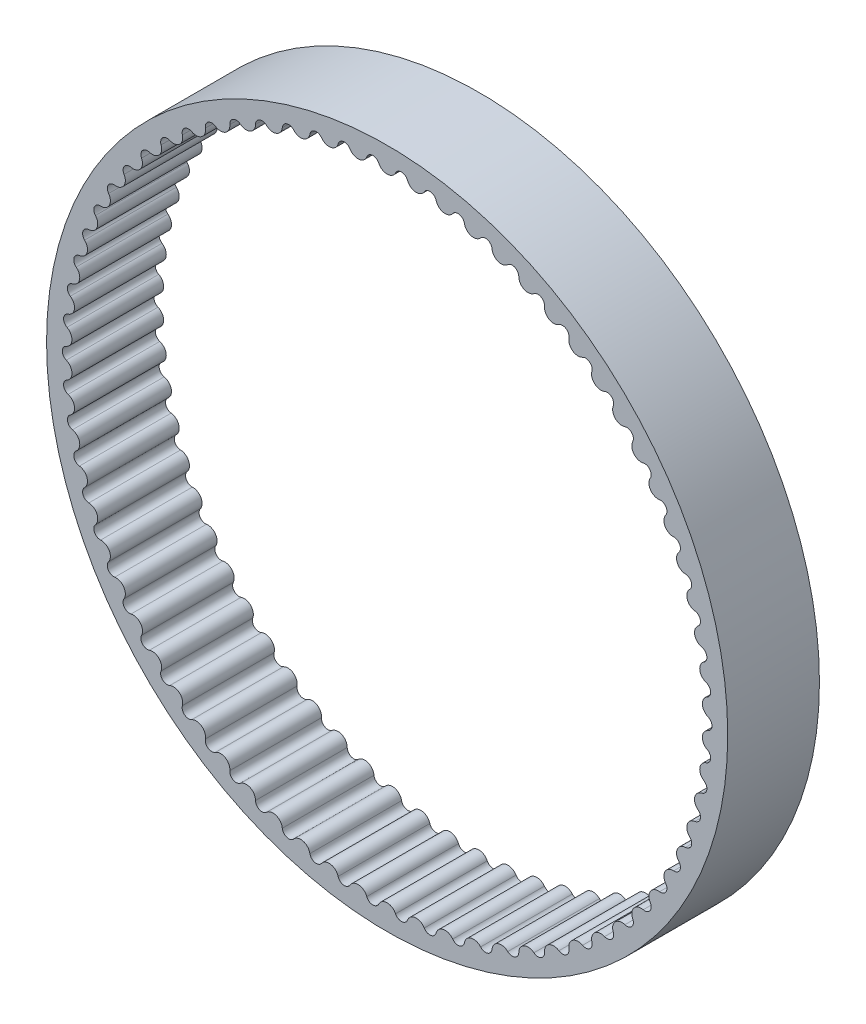
SolidWorks part; units mm, degrees
ref_plane "Front Plane" through (0, 0, 0) normal (0, 0, 1) x (1, 0, 0)
ref_plane "Top Plane" through (0, 0, 0) normal (0, 1, 0) x (1, 0, 0)
ref_plane "Right Plane" through (0, 0, 0) normal (1, 0, 0) x (0, 0, -1)
sketch "Sketch1" plane through (0, 0, 0) normal (0, 0, 1) x (1, 0, 0)
  line L0 (0, 0) -> (0, 21.2517) construction
  line L1 (0, 0) -> (1.905, 21.1662) construction
  line L2 (0, 0) -> (3.7946, 20.9102) construction
  line L3 (-1.905, 21.1662) -> (0, 0) construction
  circle A0 centre (0, 0) radius 22.2817
  circle A1 centre (0, 0) radius 20.6417
  circle A2 centre (0, 0) radius 21.2517 construction
  circle A10 centre (0, 21.2517) radius 0.61
  circle A101 centre (1.905, 21.1662) radius 0.61
  circle A102 centre (0.9344, 20.8052) radius 0.4256
  circle A103 centre (-0.9344, 20.8052) radius 0.4256
  circle A104 centre (-1.905, 21.1662) radius 0.61
  point P16 (-1.8503, 20.5586)
  point P17 (0, 20.6417)
  point P77 (0, 0)
  dimension "OD" = 44.5634
  dimension "Tooth Diameter" = 1.22
  dimension "Belt Thickness" = 1.64
  dimension "Angle" = 5.143
  dimension "D3" = 5.143
sketch "Sketch2" plane through (0, 0, 0) normal (0, 0, 1) x (1, 0, 0)
  circle A0 centre (0, 0) radius 20.6417 construction
  circle A1 centre (0, 0) radius 22.2817 construction
  circle A2 centre (0, 0) radius 20.6417
  circle A3 centre (0, 0) radius 22.2817
extrude "Boss-Extrude1" add sketch "Sketch2" along normal mid plane 6
sketch "Sketch3" plane through (0, 0, 0) normal (0, 0, 1) x (1, 0, 0)
  circle A0 centre (0, 0) radius 20.6417 construction
  circle A1 centre (1.905, 21.1662) radius 0.61 construction
  circle A2 centre (0.9344, 20.8052) radius 0.4256 construction
  circle A3 centre (0, 21.2517) radius 0.61 construction
  arc A4 (1.8503, 20.5586) -> (0, 20.6417) centre (0, 0) ccw
  arc A5 (1.3333, 20.9535) -> (1.8503, 20.5586) centre (1.905, 21.1662) ccw
  arc A6 (1.3333, 20.9535) -> (0.5504, 20.9887) centre (0.9344, 20.8052) ccw
  arc A7 (0, 20.6417) -> (0.5504, 20.9887) centre (0, 21.2517) ccw
extrude "Cut-Extrude1" cut sketch "Sketch3" against normal through all both and the other way through all
pattern_circular "CirPattern3" count 70 over 360 about axis through (0, 0, 3) along (0, 0, -1) of "Cut-Extrude1"
ref_axis "Center Axis 1" through (0, 0, 3) along (0, 0, -1)
equation "\"D3@Sketch1\" = \"Angle@Sketch1\""
